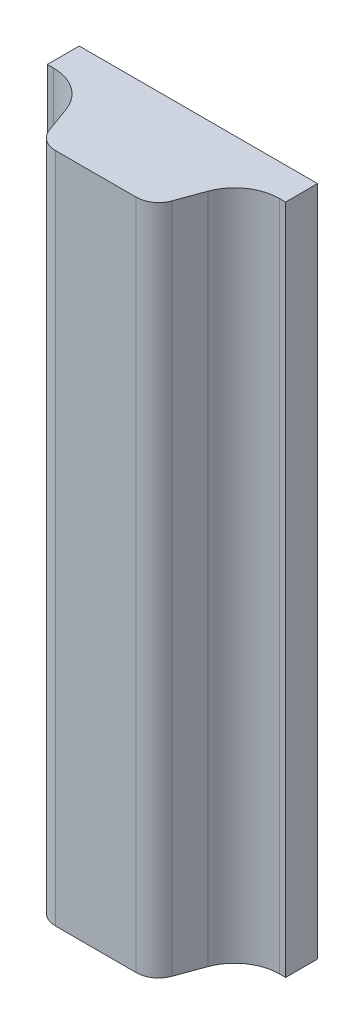
SolidWorks part; units mm, degrees
ref_plane "前视基准面" through (0, 0, 0) normal (0, 0, 1) x (1, 0, 0)
ref_plane "上视基准面" through (0, 0, 0) normal (0, 1, 0) x (1, 0, 0)
ref_plane "右视基准面" through (0, 0, 0) normal (1, 0, 0) x (0, 0, -1)
other "Configuration Table"
sketch "草图1" plane through (0, 0, 0) normal (0, 1, 0) x (1, 0, 0)
  line L0 (4.1811, -0.3462) -> (4.2666, -0.1111)
  line L1 (3.0853, -0.3462) -> (2.9997, -0.1111)
  line L2 (2.5685, 0.4376) -> (2.5685, 0.1521)
  line L3 (4.6978, 0.4376) -> (2.5685, 0.4376)
  line L4 (4.6978, 0.1521) -> (4.6978, 0.4376)
  line L5 (3.2732, -0.4777) -> (3.9931, -0.4777)
  line L6 (4.6425, 0.1521) -> (4.6978, 0.1521)
  line L7 (2.6238, 0.1521) -> (2.5685, 0.1521)
  arc A0 (3.9931, -0.4777) -> (4.1811, -0.3462) centre (3.9931, -0.2777) ccw
  arc A1 (3.0853, -0.3462) -> (3.2732, -0.4777) centre (3.2732, -0.2777) ccw
  arc A2 (2.9997, -0.1111) -> (2.6238, 0.1521) centre (2.6238, -0.2479) ccw
  arc A3 (4.6425, 0.1521) -> (4.2666, -0.1111) centre (4.6425, -0.2479) ccw
extrude "凸台-拉伸1" add sketch "草图1" along normal blind 6
sketch "草图2" plane through (0, 0, -0.4376) normal (0, 0, -1) x (-1, 0, 0)
  line L0 (-3.6332, 6) -> (-3.6332, 0)
  line L1 (-4.6978, 6) -> (-2.5685, 6) construction
  line L2 (-4.6978, 0) -> (-2.5685, 0) construction
